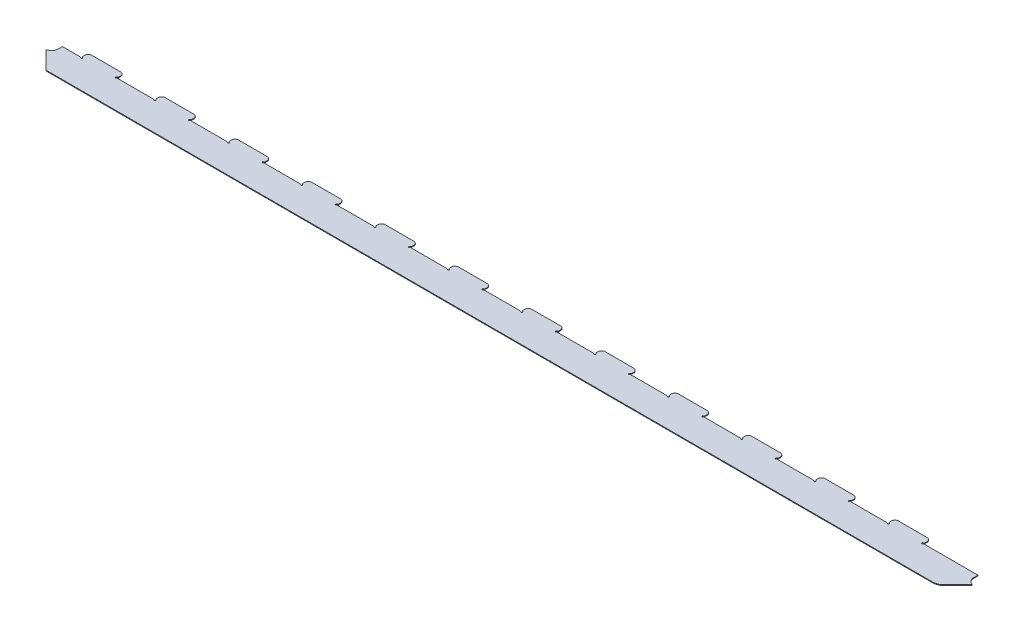
SolidWorks part; units mm, degrees
material "Copper"
ref_plane "Front Plane" through (0, 0, 0) normal (0, 0, 1) x (1, 0, 0)
ref_plane "Top Plane" through (0, 0, 0) normal (0, 1, 0) x (1, 0, 0)
ref_plane "Right Plane" through (0, 0, 0) normal (1, 0, 0) x (0, 0, -1)
ref_plane "Slot Pattern Midplane" through (-5.125, 0, 0) normal (1, 0, 0) x (0, 0, -1)
ref_plane "Near Cell Divider Plane" through (-117.875, 0, 0) normal (1, 0, 0) x (0, 0, -1)
sketch "Sketch1" plane through (0, 0, 0) normal (0, 1, 0) x (1, 0, 0)
  line L0 (-178.465, 0) -> (-175.705, 0) construction
  line L2 (-123.5319, -9.1716) -> (-121.2892, -11.4142)
  line L3 (-119.875, -12) -> (-119.375, -12)
  line L4 (-118.375, -8.5) -> (-118.375, -11)
  line L5 (-55, 0) -> (55, 0) construction
  line L6 (-117.875, 42.345) -> (-117.875, -3.6226) construction
  line L7 (-117.875, -55) -> (-117.875, 55) construction
  line L10 (-122.875, 0.5657) -> (-122.875, 1)
  line L11 (-121.875, 2) -> (-117.875, 2)
  line L13 (-117.875, 2) -> (-117.875, -8)
  line L14 (-126.3603, -8) -> (-128.125, -8)
  line L15 (-128.125, -8) -> (-128.125, 0)
  line L16 (-128.125, 0) -> (-123.1222, 0)
  arc A0 (-121.2892, -11.4142) -> (-119.875, -12) centre (-119.875, -10) ccw
  arc A1 (-119.375, -12) -> (-118.375, -11) centre (-119.375, -11) ccw
  arc A2 (-117.875, -8) -> (-118.375, -8.5) centre (-117.875, -8.5) ccw
  arc A3 (-122.875, 1) -> (-121.875, 2) centre (-121.875, 1) cw
  arc A4 (-126.3603, -8) -> (-123.5319, -9.1716) centre (-126.3603, -12) cw
  arc A5 (-122.8241, -0.1333) -> (-122.6083, 0.1886) centre (-122.675, 0) ccw
  arc A6 (-122.8241, -0.1333) -> (-123.1222, 0) centre (-123.1222, -0.4) ccw
  arc A7 (-122.6083, 0.1886) -> (-122.875, 0.5657) centre (-122.475, 0.5657) cw
  point P27 (-124.7034, -8)
  point P32 (-122.875, 0)
  dimension "D4" = 2
  dimension "D5" = 1
  dimension "D2" = 1
  dimension "D9" = 4
  dimension "D14" = 0.4
  dimension "D15" = 0.2
  dimension "D1" = 1
  dimension "D3" = 2
  dimension "D7" = 12
  dimension "D8" = 10
  dimension "D6" = 8
  dimension "D11" = 20.5
  dimension "D12" = 45
  dimension "D13" = 2
extrude "Boss-Extrude1" add sketch "Sketch1" along normal blind 0.2032 contours A7 A5 A6 L16 L15 L14 L13 L11 A3 L10 | L15 L16 A6 A5 A7 L10 A3 L11 L13 A2 L4 A1 L3 A0 L2 A4 L14 region at (-122.4079, 0, 4.4567)
mirror "Mirror1" about plane through (-117.875, 0, 0) normal (1, 0, 0) of "Boss-Extrude1"
pattern_linear "LPattern1" count 12 spacing 20.5 along (1, 0, 0) of "Boss-Extrude1", "Mirror1"
sketch "Sketch2" plane through (0, 0, 0) normal (0, 1, 0) x (1, 0, 0)
  line L0 (-144.1834, 0) -> (-44.5328, 0) construction
  line L5 (-5.125, 93.9342) -> (-5.125, 30.3173) construction
  line L6 (-128.125, -8) -> (-128.125, 0) construction
  line L7 (-0.1118, 0) -> (0.1118, 0) construction
  line L9 (-5.125, -55) -> (-5.125, 55) construction
  line L16 (116.1103, -8) -> (117.875, -8) construction
  line L17 (127.875, 0) -> (117.875, 0)
  line L18 (127.875, 0) -> (127.875, -8)
  line L19 (127.875, -8) -> (117.875, -8)
  line L20 (117.875, 0) -> (117.875, -8)
  line L21 (117.875, -8) -> (117.875, 0) construction
  dimension "D1" = 256
extrude "Boss-Extrude3" add sketch "Sketch2" along normal up to surface (0.2032 mm away) separate body up to face at (-117.875, 0.2032, 5.0816)
sketch "Sketch3" plane through (0, 0, 0) normal (0, 1, 0) x (1, 0, 0)
  line L0 (-129.4452, -3.2582) -> (-123.5319, -9.1716)
  line L1 (113.2819, -9.1716) -> (111.0392, -11.4142) construction
  line L3 (-128.125, -1.2941) -> (-128.125, -8)
  line L5 (-128.125, -8) -> (-126.3603, -8)
  line L6 (129.1952, -3.2582) -> (125.3321, -7.1213)
  line L10 (123.2108, -8) -> (127.875, -8)
  line L11 (127.875, -8) -> (127.875, -1.2941)
  line L13 (127.875, -8) -> (127.875, 0) construction
  line L14 (117.875, -8) -> (127.875, -8) construction
  line L15 (-126.3603, -8) -> (-128.125, -8) construction
  line L16 (-128.125, -8) -> (-128.125, 0) construction
  line L18 (-129.8191, -1.2941) -> (129.5691, -1.2941) construction
  line L19 (-200144.1834, 0) -> (199955.4672, 0) construction
  line L21 (-123.5319, -9.1716) -> (-121.2892, -11.4142) construction
  arc A4 (123.2108, -8) -> (125.3321, -7.1213) centre (123.2108, -5) ccw
  arc A5 (-128.125, -1.2941) -> (-129.3582, -2.9243) centre (-129.8191, -1.2941) cw
  arc A6 (-129.4452, -3.2582) -> (-129.3582, -2.9243) centre (-129.3038, -3.1168) cw
  arc A8 (127.875, -1.2941) -> (129.1082, -2.9243) centre (129.5691, -1.2941) ccw
  arc A9 (129.1082, -2.9243) -> (129.1952, -3.2582) centre (129.0538, -3.1168) cw
  arc A14 (-123.5319, -9.1716) -> (-126.3603, -8) centre (-126.3603, -12) ccw construction
  arc A15 (-123.5319, -9.1716) -> (-126.3603, -8) centre (-126.3603, -12) ccw
  dimension "D1" = 1.6941
  dimension "D2" = 0.2
  dimension "D4" = 3
  dimension "D5" = 1.1788
  dimension "D6" = 1.1788
  dimension "D3" = 1.2941
extrude "Boss-Extrude4" add sketch "Sketch3<3>" along normal up to surface (0.2032 mm away) separate body contours A5 A6 L0 L3 | L11 L6 | A5 L3 region at (-128.5894, 0, 3.2237) region at (128.3394, 0, 3.2237) up to face at (-117.875, 0.2032, 5.0816)
sketch "Sketch3<3>" plane through (0, 0, 0) normal (0, 1, 0) x (1, 0, 0) same geometry as "Sketch3"
extrude "Cut-Extrude2" cut sketch "Sketch3" along normal through all contours L0 L3 L5 | A4 L10 L11 L6 region at (-126.8633, 0, 6.9362) region at (126.659, 0, 6.8902)
combine bodies "Combine1" operation type add bodies to combine 120 113 112 111 110 109 108 107 106 105 104 103 121 125 126 125
sketch "Sketch4" plane through (0, 0, 0) normal (0, 0, 1) x (1, 0, 0)
  line L0 (-129.5038, 0) -> (-129.5038, 0.2032)
  line L1 (129.2538, 0) -> (-129.5038, 0)
  line L2 (-129.5038, 0.2032) -> (129.2538, 0.2032)
  line L3 (-129.5038, 0) -> (-129.5038, 0.2032)
  line L4 (-129.5038, 0.2032) -> (-129.3582, 0.2032)
  line L6 (-129.3582, 0.2032) -> (-128.125, 0.2032)
  line L10 (-128.125, 0.2032) -> (-123.1222, 0.2032)
  line L12 (-123.1222, 0.2032) -> (-122.875, 0.2032)
  line L14 (-122.875, 0.2032) -> (-121.875, 0.2032)
  line L16 (-121.875, 0.2032) -> (-113.875, 0.2032)
  line L18 (-113.875, 0.2032) -> (-112.875, 0.2032)
  line L20 (-112.875, 0.2032) -> (-112.6278, 0.2032)
  line L22 (-112.6278, 0.2032) -> (-102.6222, 0.2032)
  line L36 (-102.6222, 0.2032) -> (-102.375, 0.2032)
  line L38 (-102.375, 0.2032) -> (-101.375, 0.2032)
  line L40 (-101.375, 0.2032) -> (-93.375, 0.2032)
  line L42 (-93.375, 0.2032) -> (-92.375, 0.2032)
  line L44 (-92.375, 0.2032) -> (-92.1278, 0.2032)
  line L46 (-92.1278, 0.2032) -> (-82.1222, 0.2032)
  line L48 (-82.1222, 0.2032) -> (-81.875, 0.2032)
  line L50 (-81.875, 0.2032) -> (-80.875, 0.2032)
  line L52 (-80.875, 0.2032) -> (-72.875, 0.2032)
  line L54 (-72.875, 0.2032) -> (-71.875, 0.2032)
  line L56 (-71.875, 0.2032) -> (-71.6278, 0.2032)
  line L58 (-71.6278, 0.2032) -> (-61.6222, 0.2032)
  line L60 (-61.6222, 0.2032) -> (-61.375, 0.2032)
  line L62 (-61.375, 0.2032) -> (-60.375, 0.2032)
  line L64 (-60.375, 0.2032) -> (-52.375, 0.2032)
  line L66 (-52.375, 0.2032) -> (-51.375, 0.2032)
  line L68 (-51.375, 0.2032) -> (-51.1278, 0.2032)
  line L70 (-51.1278, 0.2032) -> (-41.1222, 0.2032)
  line L72 (-41.1222, 0.2032) -> (-40.875, 0.2032)
  line L74 (-40.875, 0.2032) -> (-39.875, 0.2032)
  line L76 (-39.875, 0.2032) -> (-31.875, 0.2032)
  line L78 (-31.875, 0.2032) -> (-30.875, 0.2032)
  line L80 (-30.875, 0.2032) -> (-30.6278, 0.2032)
  line L82 (-30.6278, 0.2032) -> (-20.6222, 0.2032)
  line L84 (-20.6222, 0.2032) -> (-20.375, 0.2032)
  line L86 (-20.375, 0.2032) -> (-19.375, 0.2032)
  line L88 (-19.375, 0.2032) -> (-11.375, 0.2032)
  line L90 (-11.375, 0.2032) -> (-10.375, 0.2032)
  line L92 (-10.375, 0.2032) -> (-10.1278, 0.2032)
  line L94 (-10.1278, 0.2032) -> (-0.1222, 0.2032)
  line L96 (-0.1222, 0.2032) -> (0.125, 0.2032)
  line L98 (0.125, 0.2032) -> (1.125, 0.2032)
  line L100 (1.125, 0.2032) -> (9.125, 0.2032)
  line L102 (9.125, 0.2032) -> (10.125, 0.2032)
  line L104 (10.125, 0.2032) -> (10.3722, 0.2032)
  line L106 (10.3722, 0.2032) -> (20.3778, 0.2032)
  line L108 (20.3778, 0.2032) -> (20.625, 0.2032)
  line L110 (20.625, 0.2032) -> (21.625, 0.2032)
  line L112 (21.625, 0.2032) -> (29.625, 0.2032)
  line L114 (29.625, 0.2032) -> (30.625, 0.2032)
  line L116 (30.625, 0.2032) -> (30.8722, 0.2032)
  line L118 (30.8722, 0.2032) -> (40.8778, 0.2032)
  line L120 (40.8778, 0.2032) -> (41.125, 0.2032)
  line L122 (41.125, 0.2032) -> (42.125, 0.2032)
  line L124 (42.125, 0.2032) -> (50.125, 0.2032)
  line L126 (50.125, 0.2032) -> (51.125, 0.2032)
  line L128 (51.125, 0.2032) -> (51.3722, 0.2032)
  line L130 (51.3722, 0.2032) -> (61.3778, 0.2032)
  line L132 (61.3778, 0.2032) -> (61.625, 0.2032)
  line L134 (61.625, 0.2032) -> (62.625, 0.2032)
  line L136 (62.625, 0.2032) -> (70.625, 0.2032)
  line L138 (70.625, 0.2032) -> (71.625, 0.2032)
  line L140 (71.625, 0.2032) -> (71.8722, 0.2032)
  line L142 (71.8722, 0.2032) -> (81.8778, 0.2032)
  line L144 (81.8778, 0.2032) -> (82.125, 0.2032)
  line L146 (82.125, 0.2032) -> (83.125, 0.2032)
  line L148 (83.125, 0.2032) -> (91.125, 0.2032)
  line L150 (91.125, 0.2032) -> (92.125, 0.2032)
  line L152 (92.125, 0.2032) -> (92.3722, 0.2032)
  line L154 (92.3722, 0.2032) -> (102.3778, 0.2032)
  line L156 (102.3778, 0.2032) -> (102.625, 0.2032)
  line L158 (102.625, 0.2032) -> (103.625, 0.2032)
  line L160 (103.625, 0.2032) -> (111.625, 0.2032)
  line L162 (111.625, 0.2032) -> (112.625, 0.2032)
  line L164 (112.625, 0.2032) -> (112.8722, 0.2032)
  line L166 (112.8722, 0.2032) -> (127.875, 0.2032)
  line L168 (127.875, 0.2032) -> (129.1082, 0.2032)
  line L170 (129.1082, 0.2032) -> (129.2538, 0.2032)
  line L172 (129.2538, 0.2032) -> (129.2538, 0)
  line L174 (129.2538, 0) -> (129.1082, 0)
  line L176 (129.1082, 0) -> (127.875, 0)
  line L178 (127.875, 0) -> (112.8722, 0)
  line L180 (112.8722, 0) -> (112.625, 0)
  line L182 (112.625, 0) -> (111.625, 0)
  line L184 (111.625, 0) -> (103.625, 0)
  line L186 (103.625, 0) -> (102.625, 0)
  line L188 (102.625, 0) -> (102.3778, 0)
  line L190 (102.3778, 0) -> (92.3722, 0)
  line L192 (92.3722, 0) -> (92.125, 0)
  line L194 (92.125, 0) -> (91.125, 0)
  line L196 (91.125, 0) -> (83.125, 0)
  line L198 (83.125, 0) -> (82.125, 0)
  line L200 (82.125, 0) -> (81.8778, 0)
  line L202 (81.8778, 0) -> (71.8722, 0)
  line L204 (71.8722, 0) -> (71.625, 0)
  line L206 (71.625, 0) -> (70.625, 0)
  line L208 (70.625, 0) -> (62.625, 0)
  line L210 (62.625, 0) -> (61.625, 0)
  line L212 (61.625, 0) -> (61.3778, 0)
  line L214 (61.3778, 0) -> (51.3722, 0)
  line L216 (51.3722, 0) -> (51.125, 0)
  line L218 (51.125, 0) -> (50.125, 0)
  line L220 (50.125, 0) -> (42.125, 0)
  line L222 (42.125, 0) -> (41.125, 0)
  line L224 (41.125, 0) -> (40.8778, 0)
  line L226 (40.8778, 0) -> (30.8722, 0)
  line L228 (30.8722, 0) -> (30.625, 0)
  line L230 (30.625, 0) -> (29.625, 0)
  line L232 (29.625, 0) -> (21.625, 0)
  line L234 (21.625, 0) -> (20.625, 0)
  line L236 (20.625, 0) -> (20.3778, 0)
  line L238 (20.3778, 0) -> (10.3722, 0)
  line L240 (10.3722, 0) -> (10.125, 0)
  line L242 (10.125, 0) -> (9.125, 0)
  line L244 (9.125, 0) -> (1.125, 0)
  line L246 (1.125, 0) -> (0.125, 0)
  line L248 (0.125, 0) -> (-0.1222, 0)
  line L250 (-0.1222, 0) -> (-10.1278, 0)
  line L252 (-10.1278, 0) -> (-10.375, 0)
  line L254 (-10.375, 0) -> (-11.375, 0)
  line L256 (-11.375, 0) -> (-19.375, 0)
  line L258 (-19.375, 0) -> (-20.375, 0)
  line L260 (-20.375, 0) -> (-20.6222, 0)
  line L262 (-20.6222, 0) -> (-30.6278, 0)
  line L264 (-30.6278, 0) -> (-30.875, 0)
  line L266 (-30.875, 0) -> (-31.875, 0)
  line L268 (-31.875, 0) -> (-39.875, 0)
  line L270 (-39.875, 0) -> (-40.875, 0)
  line L272 (-40.875, 0) -> (-41.1222, 0)
  line L274 (-41.1222, 0) -> (-51.1278, 0)
  line L276 (-51.1278, 0) -> (-51.375, 0)
  line L278 (-51.375, 0) -> (-52.375, 0)
  line L280 (-52.375, 0) -> (-60.375, 0)
  line L282 (-60.375, 0) -> (-61.375, 0)
  line L284 (-61.375, 0) -> (-61.6222, 0)
  line L286 (-61.6222, 0) -> (-71.6278, 0)
  line L288 (-71.6278, 0) -> (-71.875, 0)
  line L290 (-71.875, 0) -> (-72.875, 0)
  line L292 (-72.875, 0) -> (-80.875, 0)
  line L294 (-80.875, 0) -> (-81.875, 0)
  line L296 (-81.875, 0) -> (-82.1222, 0)
  line L298 (-102.6222, 0) -> (-112.6278, 0)
  line L300 (-112.6278, 0) -> (-112.875, 0)
  line L302 (-112.875, 0) -> (-113.875, 0)
  line L304 (-113.875, 0) -> (-121.875, 0)
  line L306 (-121.875, 0) -> (-122.875, 0)
  line L308 (-122.875, 0) -> (-123.1222, 0)
  line L310 (-123.1222, 0) -> (-128.125, 0)
  line L312 (-82.1222, 0) -> (-92.1278, 0)
  line L314 (-92.1278, 0) -> (-92.375, 0)
  line L318 (-92.375, 0) -> (-93.375, 0)
  line L319 (-93.375, 0) -> (-101.375, 0)
  line L320 (-101.375, 0) -> (-102.375, 0)
  line L321 (-102.375, 0) -> (-102.6222, 0)
  line L330 (-128.125, 0) -> (-129.3582, 0)
  line L331 (-129.3582, 0) -> (-129.5038, 0)
  line L385 (129.2538, 0.2032) -> (129.2538, 0)
extrude "Cut-Extrude3" cut sketch "Sketch4" along normal through all from surface starting at face at (-107.625, 0.1016, 8)
equation "\"Cell Spacing\"= 20.5mm"
equation "\"Parallel Cells\"= 12"
equation "\"D1@Slot Pattern Midplane\" = \"Cell Spacing\" / 4"
equation "\"D1@Near Cell Divider Plane\"=\"Cell Spacing\"*((\"Parallel Cells\"-1)/2)"
equation "\"D3@LPattern1\"=\"Cell Spacing\""
equation "\"D1@LPattern1\"=\"Parallel Cells\""
equation "\"D11@Sketch1\"=\"Cell Spacing\""
equation "\"Gauge Diameter\"= 0.1019in'10 AWG solid wire"
equation "\"D1@Sketch3\"=\"Gauge Diameter\"/2 +.4"
equation "\"D6@Sketch3\"=\"D5@Sketch3\""
equation "\"D3@Sketch3\"=\"Gauge Diameter\"/2"
